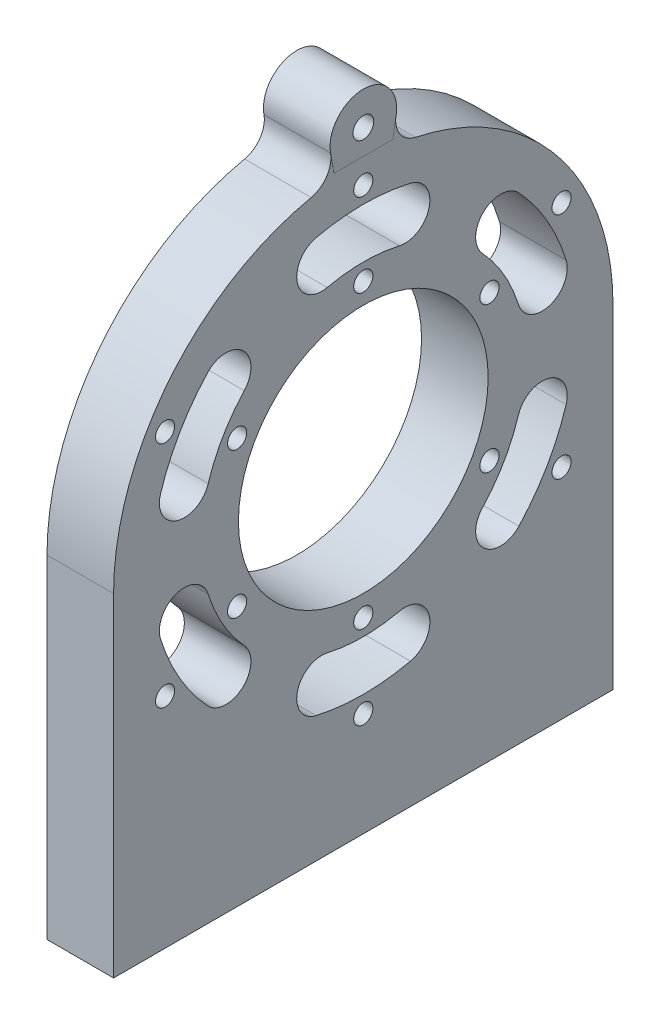
SolidWorks part; units mm, degrees
material "6061 Alloy"
ref_plane "前视基准面" through (0, 0, 0) normal (0, 0, 1) x (1, 0, 0)
ref_plane "上视基准面" through (0, 0, 0) normal (0, 1, 0) x (1, 0, 0)
ref_plane "右视基准面" through (0, 0, 0) normal (1, 0, 0) x (0, 0, -1)
sketch "草图1" plane through (0, 0, 0) normal (1, 0, 0) x (0, 0, -1)
  line L0 (-30, 0) -> (-30, -40)
  line L1 (-30, -40) -> (30, -40)
  line L2 (30, -40) -> (30, 0)
  arc A0 (-6.265, 29.3385) -> (6.265, 29.3385) centre (0, 0) ccw
  circle A1 centre (0, 0) radius 15
  circle A3 centre (0, 33.5) radius 1.25
  arc A4 (3.938, 32.7985) -> (-3.938, 32.7985) centre (0, 33.5) ccw
  arc A5 (3.938, 32.7985) -> (6.265, 29.3385) centre (6.8915, 32.2724) ccw
  arc A6 (-6.265, 29.3385) -> (-3.938, 32.7985) centre (-6.8915, 32.2724) ccw
  circle B0 centre (23.8157, -13.75) radius 1.15
  circle B1 centre (15.1554, -8.75) radius 1.15
  circle B2 centre (0, 0) radius 15
  arc B3 (18.6319, 5.7534) -> (24.3648, 7.5237) centre (21.4984, 6.6386) ccw
  arc B4 (18.6319, 5.7534) -> (14.2986, 13.259) centre (0, 0) ccw
  arc B5 (18.6981, 17.3387) -> (14.2986, 13.259) centre (16.4984, 15.2988) ccw
  arc B6 (24.3648, 7.5237) -> (18.6981, 17.3387) centre (0, 0) ccw
  arc B7 (-4.3333, -19.0124) -> (-5.6667, -24.8624) centre (-5, -21.9374) ccw
  arc B8 (-4.3333, -19.0124) -> (4.3333, -19.0124) centre (0, 0) ccw
  arc B9 (5.6667, -24.8624) -> (4.3333, -19.0124) centre (5, -21.9374) ccw
  arc B10 (-5.6667, -24.8624) -> (5.6667, -24.8624) centre (0, 0) ccw
  arc B11 (-18.6319, -5.7534) -> (-24.3648, -7.5237) centre (-21.4984, -6.6386) ccw
  arc B12 (-18.6319, -5.7534) -> (-14.2986, -13.259) centre (0, 0) ccw
  arc B13 (-18.6981, -17.3387) -> (-14.2986, -13.259) centre (-16.4984, -15.2988) ccw
  arc B14 (-24.3648, -7.5237) -> (-18.6981, -17.3387) centre (0, 0) ccw
  arc B15 (4.3333, 19.0124) -> (5.6667, 24.8624) centre (5, 21.9374) ccw
  arc B16 (4.3333, 19.0124) -> (-4.3333, 19.0124) centre (0, 0) ccw
  arc B17 (-5.6667, 24.8624) -> (-4.3333, 19.0124) centre (-5, 21.9374) ccw
  arc B18 (5.6667, 24.8624) -> (-5.6667, 24.8624) centre (0, 0) ccw
  circle B19 centre (15.1554, 8.75) radius 1.15
  arc B20 (-14.2986, 13.259) -> (-18.6981, 17.3387) centre (-16.4984, 15.2988) ccw
  arc B21 (-14.2986, 13.259) -> (-18.6319, 5.7534) centre (0, 0) ccw
  arc B22 (-24.3648, 7.5237) -> (-18.6319, 5.7534) centre (-21.4984, 6.6386) ccw
  arc B23 (-18.6981, 17.3387) -> (-24.3648, 7.5237) centre (0, 0) ccw
  circle B24 centre (0, -17.5) radius 1.15
  circle B25 centre (-23.8157, -13.75) radius 1.15
  circle B26 centre (-15.1554, -8.75) radius 1.15
  circle B27 centre (-23.8157, 13.75) radius 1.15
  circle B28 centre (23.8157, 13.75) radius 1.15
  circle B29 centre (0, 17.5) radius 1.15
  circle B30 centre (0, 27.5) radius 1.15
  circle B31 centre (-15.1554, 8.75) radius 1.15
  circle B32 centre (0, -27.5) radius 1.15
  arc B33 (24.3648, -7.5237) -> (18.6319, -5.7534) centre (21.4984, -6.6386) ccw
  arc B34 (18.6981, -17.3387) -> (24.3648, -7.5237) centre (0, 0) ccw
  arc B35 (14.2986, -13.259) -> (18.6981, -17.3387) centre (16.4984, -15.2988) ccw
  arc B36 (14.2986, -13.259) -> (18.6319, -5.7534) centre (0, 0) ccw
  dimension "D1" = 60
  dimension "D2" = 2.5
  dimension "D3" = 6
  dimension "D4" = 8
  dimension "D5" = 3
  dimension "D6" = 40
sketch_block_instance "块-外骨骼脊髓盘草图-1"
sketch_block "块-外骨骼脊髓盘草图"
extrude "凸台-拉伸1" add sketch "草图1" along normal mid plane 8 contours A6 A0 A5 A4 B32 B31 B30 B29 B28 B27 B26 B25 B24 B23 B20 B21 B22 B19 B18 B15 B16 B17 B14 B11 B12 B13 B10 B7 B8 B9 B6 B3 B4 B5 B1 | A0 L0 L1 L2 region at (0, -30.4172, 0) region at (0, 18.3006, 22.6212)
sketch "草图2" plane through (0, -40, 0) normal (0, -1, 0) x (1, 0, 0)
  line L1 (4, 30) -> (4, -30) construction
  circle A0 centre (0, 22.5) radius 1.5
  circle A1 centre (0, -22.5) radius 1.5
  circle A2 centre (0, 0) radius 1.5
  dimension "D1" = 3
  dimension "D2" = 3
  dimension "D3" = 45
  dimension "D7" = 3
  dimension "D4" = 22.5
  dimension "D5" = 4
  dimension "D6" = 4
hole_wizard "M3 螺纹孔1" positions "3D草图1" profile "草图3" tap size "M3" standard "GB"
sketch3d "3D草图1"
  point P0 (0, -40, 22.5)
  point P3 (0, -40, 0)
  point P6 (0, -40, -22.5)
sketch "草图3" plane through (0, -40, 22.5) normal (1, 0, 0) x (0, 0, -1)
  line L0 (0, 0) -> (0, 8.2511)
  line L1 (0, 8.2511) -> (1.25, 7.5)
  line L2 (1.25, 7.5) -> (1.25, 0)
  line L5 (1.25, 0) -> (0, 0)
  line L10 (0, 8.2511) -> (-1.25, 7.5) construction
  line L11 (0, -6.35) -> (0, 107.95) construction
  dimension "螺纹孔钻头直径" = 2.5
  dimension "螺纹孔钻头深度" = 7.5
  dimension "导头角度" = 118
cosmetic thread "孔螺蚊线1" parameters "D1"=6, "D2"=3
cosmetic thread "孔螺蚊线2" parameters "D1"=6, "D2"=3
cosmetic thread "孔螺蚊线3" parameters "D1"=6, "D2"=3
sketch "Sketch1" plane through (4, 0, 0) normal (1, 0, 0) x (0, 0, -1)
  line L0 (-3.938, 32.7985) -> (-3.5268, 30.4903)
  line L1 (3.938, 32.7985) -> (3.5268, 30.4903)
  line L2 (3.5268, 30.4903) -> (-3.5268, 30.4903)
  arc A0 (3.938, 32.7985) -> (-3.938, 32.7985) centre (0, 33.5) ccw construction
  arc A1 (3.938, 32.7985) -> (-3.938, 32.7985) centre (0, 33.5) ccw
  circle A2 centre (0, 33.5) radius 1.25 construction
  circle A3 centre (0, 33.5) radius 1.25
extrude "Boss-Extrude1" add sketch "Sketch1" along normal blind 0.01
extrude "Boss-Extrude2" add sketch "Sketch1<2>" along normal blind 0.01
sketch "Sketch1<2>" plane through (4, 0, 0) normal (1, 0, 0) x (0, 0, -1) same geometry as "Sketch1"
